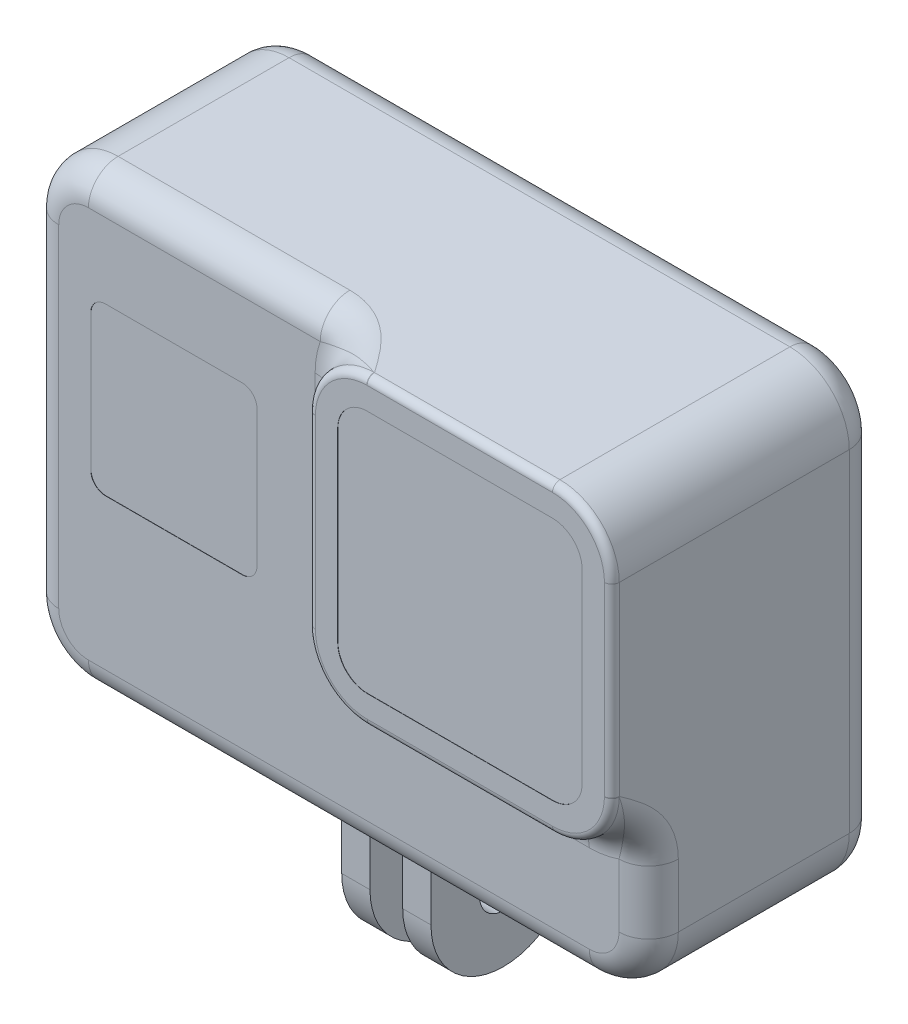
SolidWorks part; units mm, degrees
ref_plane "Front Plane" through (0, 0, 0) normal (0, 0, 1) x (1, 0, 0)
ref_plane "Top Plane" through (0, 0, 0) normal (0, 1, 0) x (1, 0, 0)
ref_plane "Right Plane" through (0, 0, 0) normal (1, 0, 0) x (0, 0, -1)
sketch "Sketch1" plane through (0, 0, 0) normal (0, 0, 1) x (1, 0, 0)
  line L1 (-33.147, -24.13) -> (33.147, -24.13)
  line L2 (-33.147, -24.13) -> (-33.147, 24.13)
  line L3 (-33.147, 24.13) -> (33.147, 24.13)
  line L4 (33.147, -24.13) -> (33.147, 24.13)
  line L5 (-33.147, -24.13) -> (33.147, 24.13) construction
  line L6 (-33.147, 24.13) -> (33.147, -24.13) construction
  point P0 (0, 0)
  dimension "D1" = 48.26
  dimension "D2" = 66.294
extrude "Boss-Extrude1" add sketch "Sketch1" along normal blind 24.638
sketch "Sketch2" plane through (0, 0, 24.638) normal (0, 0, 1) x (1, 0, 0)
  line L1 (33.147, 24.13) -> (0.635, 24.13)
  line L2 (33.147, 24.13) -> (33.147, -8.382)
  line L3 (33.147, -8.382) -> (0.635, -8.382)
  line L4 (0.635, 24.13) -> (0.635, -8.382)
  dimension "D1" = 32.512
extrude "Boss-Extrude2" add sketch "Sketch2" along normal blind 3.937
fillet "Fillet1" radius 6.35 7 edges at (33.147, -24.13, 12.319) (33.147, -8.382, 26.6065) (0.635, -8.382, 26.6065) (-33.147, -24.13, 12.319) (-33.147, 24.13, 12.319) (0.635, 24.13, 26.6065) (33.147, 24.13, 14.2875)
fillet "Fillet2" radius 3.175 20 edges at (31.2871, -22.2701, 0) (0, -24.13, 0) (-31.2871, -22.2701, 0) (-33.147, 0, 0) (-31.2871, 22.2701, 0) (0, 24.13, 0) (31.2871, 22.2701, 0) (2.4949, 22.2701, 24.638) (31.2871, -6.5221, 24.638) (16.891, -8.382, 24.638) (2.4949, -6.5221, 24.638) (-9.906, 24.13, 24.638) (-31.2871, 22.2701, 24.638) (-33.147, 0, 24.638) (-31.2871, -22.2701, 24.638) (33.147, -9.906, 24.638) (31.2871, -22.2701, 24.638) (33.147, 0, 0) (0.635, 7.874, 24.638) (0, -24.13, 24.638)
fillet "Fillet3" radius 0.7937 8 edges at (31.2871, 22.2701, 28.575) (33.147, 7.874, 28.575) (31.2871, -6.5221, 28.575) (16.891, -8.382, 28.575) (2.4949, -6.5221, 28.575) (0.635, 7.874, 28.575) (2.4949, 22.2701, 28.575) (16.891, 24.13, 28.575)
sketch "Sketch3" plane through (0, -24.13, 0) normal (0, -1, 0) x (-1, 0, 0)
  line L0 (18.288, -11.811) -> (-18.288, -11.811) construction
  line L1 (18.288, -19.558) -> (-18.288, -19.558)
  line L2 (18.288, -4.064) -> (-18.288, -4.064)
  line L4 (-26.797, 0) -> (26.797, 0) construction
  arc A0 (18.288, -19.558) -> (18.288, -4.064) centre (18.288, -11.811) ccw
  arc A1 (-18.288, -4.064) -> (-18.288, -19.558) centre (-18.288, -11.811) ccw
  point P2 (0, -11.811)
  point P7 (0, 0)
  point P8 (0, 0)
  dimension "D1" = 15.494
  dimension "D2" = 36.576
  dimension "D3" = 4.064
extrude "Cut-Extrude1" cut sketch "Sketch3" against normal blind 3.175
sketch "Sketch4" plane through (0, -20.955, 0) normal (0, -1, 0) x (-1, 0, 0)
  line L0 (18.288, -4.064) -> (-18.288, -4.064) construction
  line L1 (1.7526, -4.064) -> (-1.7526, -4.064)
  line L2 (1.7526, -4.064) -> (1.7526, -19.558)
  line L3 (1.7526, -19.558) -> (-1.7526, -19.558)
  line L4 (-1.7526, -4.064) -> (-1.7526, -19.558)
  line L5 (-18.288, -19.558) -> (18.288, -19.558) construction
  point P8 (0, -4.064)
  dimension "D1" = 3.5052
extrude "Boss-Extrude3" add sketch "Sketch4" along normal up to surface (3.175 mm away) up to face at (0, -24.13, 11.811)
sketch "Sketch5" plane through (1.7526, 0, 0) normal (1, 0, 0) x (0, 0, -1)
  line L0 (-19.558, -20.955) -> (-19.558, -32.258)
  line L1 (-19.558, -24.13) -> (-19.558, -20.955) construction
  line L2 (-4.064, -20.955) -> (-19.558, -20.955) construction
  line L3 (-4.064, -32.258) -> (-4.064, -20.955)
  line L4 (-4.064, -20.955) -> (-19.558, -20.955)
  arc A0 (-19.558, -32.258) -> (-4.064, -32.258) centre (-11.811, -32.258) ccw
  circle A1 centre (-11.811, -32.258) radius 2.54
  point P11 (-11.811, -40.005)
  dimension "D1" = 19.05
  dimension "D2" = 5.08
extrude "Boss-Extrude4" add sketch "Sketch5" along normal blind 3.0226
mirror "Mirror1" about plane through (0, 0, 0) normal (1, 0, 0) of "Boss-Extrude4"
sketch "Sketch6" plane through (0, 0, 28.575) normal (0, 0, 1) x (1, 0, 0)
  line L8 (3.8099, 17.78) -> (3.8099, -2.032)
  line L9 (6.985, -5.2071) -> (26.797, -5.2071)
  line L10 (29.972, -2.0545) -> (29.972, 17.78)
  line L11 (26.797, 20.955) -> (6.9625, 20.955)
  line L12 (3.8099, 17.78) -> (3.8099, -2.032)
  line L13 (6.985, -5.2071) -> (26.797, -5.2071)
  line L14 (29.972, -2.0545) -> (29.972, 17.78)
  line L15 (26.797, 20.955) -> (6.9625, 20.955)
  arc A12 (3.8099, -2.032) -> (6.985, -5.2071) centre (6.985, -2.032) ccw
  arc A13 (26.797, -5.2071) -> (29.9719, -2.0679) centre (26.797, -2.032) ccw
  arc A14 (29.9719, -2.0679) -> (29.972, -2.0545) centre (28.7813, -2.0545) ccw
  arc A15 (29.972, 17.78) -> (26.797, 20.955) centre (26.797, 17.78) ccw
  arc A16 (6.9625, 20.955) -> (6.9491, 20.9549) centre (6.9625, 19.7643) ccw
  arc A17 (6.9491, 20.9549) -> (3.8099, 17.78) centre (6.985, 17.78) ccw
  arc A18 (3.8099, -2.032) -> (6.985, -5.2071) centre (6.985, -2.032) ccw
  arc A19 (26.797, -5.2071) -> (29.9719, -2.0679) centre (26.797, -2.032) ccw
  arc A20 (29.9719, -2.0679) -> (29.972, -2.0545) centre (28.7813, -2.0545) ccw
  arc A21 (29.972, 17.78) -> (26.797, 20.955) centre (26.797, 17.78) ccw
  arc A22 (6.9625, 20.955) -> (6.9491, 20.9549) centre (6.9625, 19.7643) ccw
  arc A23 (6.9491, 20.9549) -> (3.8099, 17.78) centre (6.985, 17.78) ccw
  dimension "D1" = 2.3813
extrude "Cut-Extrude2" cut sketch "Sketch6" against normal blind 0.0254
sketch "Sketch7" plane through (0, 0, 0) normal (0, 0, -1) x (-1, 0, 0)
  line L8 (-27.5907, 17.78) -> (-27.5907, -17.78)
  line L9 (-26.797, -18.5738) -> (26.797, -18.5738)
  line L10 (27.5907, -17.78) -> (27.5907, 17.78)
  line L11 (26.797, 18.5738) -> (-26.797, 18.5738)
  line L12 (-27.5907, 17.78) -> (-27.5907, -17.78)
  line L13 (-26.797, -18.5738) -> (26.797, -18.5738)
  line L14 (27.5907, -17.78) -> (27.5907, 17.78)
  line L15 (26.797, 18.5738) -> (-26.797, 18.5738)
  arc A8 (-27.5907, -17.78) -> (-26.797, -18.5738) centre (-26.797, -17.78) ccw
  arc A9 (26.797, -18.5738) -> (27.5907, -17.78) centre (26.797, -17.78) ccw
  arc A10 (27.5907, 17.78) -> (26.797, 18.5738) centre (26.797, 17.78) ccw
  arc A11 (-26.797, 18.5738) -> (-27.5907, 17.78) centre (-26.797, 17.78) ccw
  arc A12 (-27.5907, -17.78) -> (-26.797, -18.5738) centre (-26.797, -17.78) ccw
  arc A13 (26.797, -18.5738) -> (27.5907, -17.78) centre (26.797, -17.78) ccw
  arc A14 (27.5907, 17.78) -> (26.797, 18.5738) centre (26.797, 17.78) ccw
  arc A15 (-26.797, 18.5738) -> (-27.5907, 17.78) centre (-26.797, 17.78) ccw
  dimension "D1" = 2.3813
extrude "Cut-Extrude3" cut sketch "Sketch7" against normal blind 0.0254
sketch "Sketch8" plane through (0, 0, 24.638) normal (0, 0, 1) x (1, 0, 0)
  line L0 (-26.797, 24.13) -> (-1.9953, 24.13) construction
  line L1 (-10.3505, 12.954) -> (-24.9555, 12.954)
  line L2 (-8.763, 11.3665) -> (-8.763, -3.2385)
  line L3 (-10.3505, -4.826) -> (-24.9555, -4.826)
  line L4 (-26.543, 11.3665) -> (-26.543, -3.2385)
  line L5 (-33.147, -17.78) -> (-33.147, 17.78) construction
  arc A0 (-24.9555, -4.826) -> (-26.543, -3.2385) centre (-24.9555, -3.2385) cw
  arc A1 (-8.763, -3.2385) -> (-10.3505, -4.826) centre (-10.3505, -3.2385) cw
  arc A2 (-10.3505, 12.954) -> (-8.763, 11.3665) centre (-10.3505, 11.3665) cw
  arc A3 (-24.9555, 12.954) -> (-26.543, 11.3665) centre (-24.9555, 11.3665) ccw
  point P14 (-8.763, 12.954)
  point P17 (-26.543, 12.954)
  dimension "D4" = 1.5875
  dimension "D1" = 17.78
  dimension "D2" = 11.176
  dimension "D3" = 6.604
extrude "Cut-Extrude4" cut sketch "Sketch8" against normal blind 0.0254
